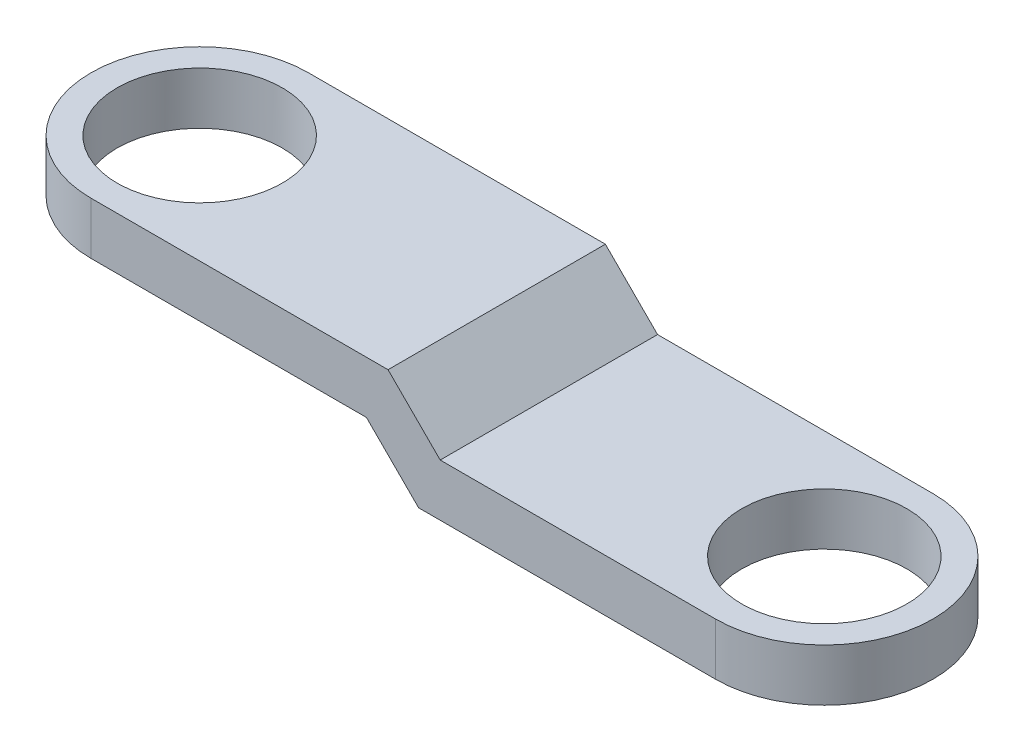
SolidWorks part; units mm, degrees
ref_plane "Front Plane" through (0, 0, 0) normal (0, 0, 1) x (1, 0, 0)
ref_plane "Top Plane" through (0, 0, 0) normal (0, 1, 0) x (1, 0, 0)
ref_plane "Right Plane" through (0, 0, 0) normal (1, 0, 0) x (0, 0, -1)
sketch "Sketch1" plane through (0, 0, 0) normal (0, 0, 1) x (1, 0, 0)
  line L0 (-3, 3) -> (3, -3)
  line L1 (0, 0) -> (0, 20.345) construction
  line L2 (3, -3) -> (35.921, -3)
  line L3 (-3, 3) -> (-35.921, 3)
  point P2 (38.1772, -3)
  point P3 (0, 0)
  dimension "D1" = 45
  dimension "D2" = 6
  dimension "D3" = 71.842
extrude "Extrude-Thin1" add sketch "Sketch1" along normal mid plane 25 thin thin type mid plane wall 6
sketch "Sketch3" plane through (0, 6, 0) normal (0, 1, 0) x (1, 0, 0)
  line L0 (-35.921, -12.5) -> (-35.921, 12.5) construction
  line L1 (-35.921, 12.5) -> (-35.921, -12.5)
  line L2 (35.921, 12.5) -> (35.921, -12.5)
  arc A0 (-35.921, 12.5) -> (-35.921, -12.5) centre (-35.921, 0) ccw
  arc A1 (35.921, -12.5) -> (35.921, 12.5) centre (35.921, 0) ccw
  line M3 (-35.921, 12.5) -> (-35.921, -12.5)
extrude "Boss-Extrude1" add sketch "Sketch3" against normal up to surface (6 mm away) contours A0 M3 region at (-41.2262, 6, 0) up to face at (-20.0818, 0, 0)
extrude "Boss-Extrude2" add sketch "Sketch3<3>" along normal up to surface (-6 mm away) from surface contours L2 A1 region at (41.2262, 6, 0) up to face at (20.0818, 0, 0) starting at face at (18.8392, -6, 0)
sketch "Sketch3<3>" plane through (0, 6, 0) normal (0, 1, 0) x (1, 0, 0) same geometry as "Sketch3"
sketch "Sketch4" plane through (0, 6, 0) normal (0, 1, 0) x (1, 0, 0)
  arc A0 (-35.921, 12.5) -> (-35.921, -12.5) centre (-35.921, 0) ccw construction
  circle A1 centre (-35.921, 0) radius 9.5
  circle A2 centre (35.921, 0) radius 9.5
  arc A3 (35.921, -12.5) -> (35.921, 12.5) centre (35.921, 0) ccw construction
  dimension "D1" = 19
  dimension "D2" = 19
extrude "Cut-Extrude1" cut sketch "Sketch4" against normal through all
equation "\"D3@Sketch1\"=sqr(8)"
